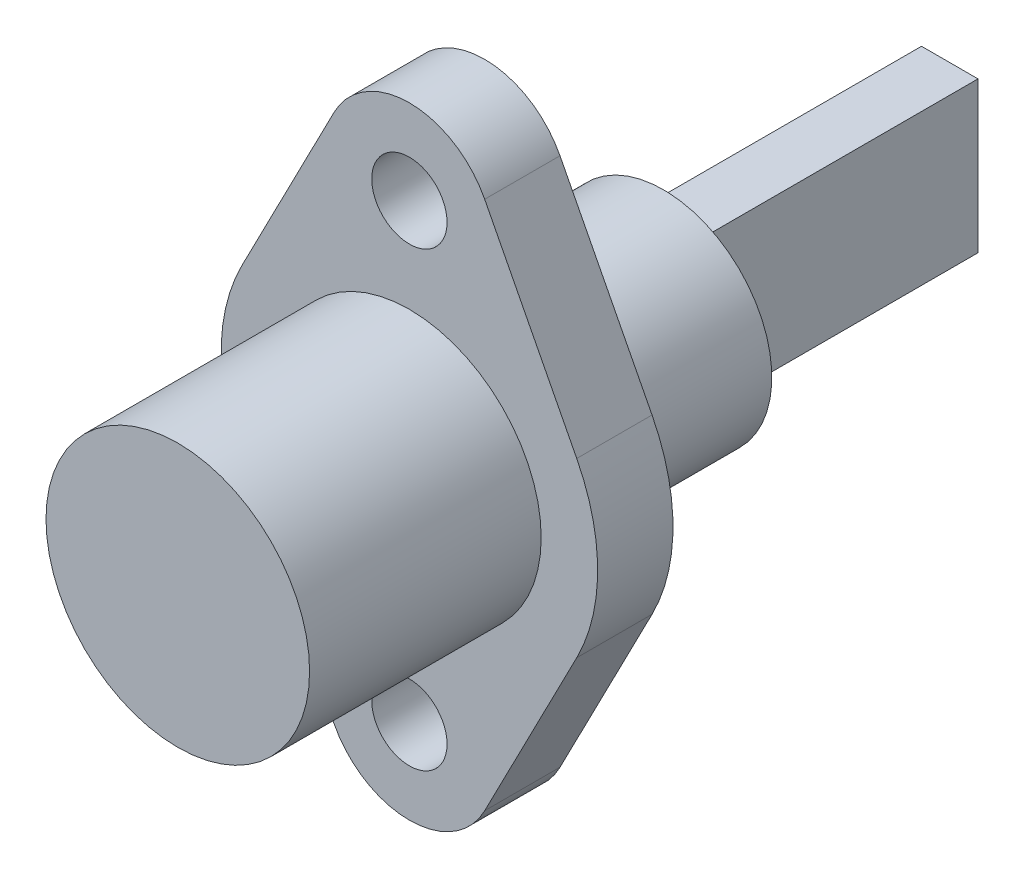
SolidWorks part; units mm, degrees
material "Custom Plastic"
ref_plane "X-Y Datum" through (0, 0, 0) normal (0, 0, 1) x (1, 0, 0)
ref_plane "X-Z Datum" through (0, 0, 0) normal (0, 1, 0) x (1, 0, 0)
ref_plane "Y-Z Datum" through (0, 0, 0) normal (1, 0, 0) x (0, 0, -1)
sketch "Sketch1" plane through (0, 0, 0) normal (0, 0, 1) x (1, 0, 0)
  line L0 (0, 17) -> (0, -17) construction
  line L1 (-10, 0) -> (10, 0) construction
  line L2 (-3.7696, 14.5084) -> (-8.8878, 4.5833)
  line L3 (3.7696, 14.5084) -> (8.8878, 4.5833)
  line L4 (3.7696, -14.5084) -> (8.8878, -4.5833)
  line L5 (-3.7696, -14.5084) -> (-8.8878, -4.5833)
  line L6 (0, 12) -> (0, -12) construction
  circle A0 centre (0, 0) radius 10
  circle A5 centre (0, 12) radius 2
  circle A6 centre (0, -12) radius 2
  circle A7 centre (0, 12) radius 4.5
  circle A8 centre (0, -12) radius 4.5
  point P4 (0, 0)
  point P8 (0, 0)
  point P23 (-4.7908, 14.0744)
  point P24 (-3.3142, -14.2597)
  point P26 (0, 0)
  dimension "D3" = 4
  dimension "D5" = 24
  dimension "D1" = 34
  dimension "D2" = 20
  dimension "D4" = 24
  dimension "D6" = 2.5
extrude "Boss-Extrude1" add sketch "Sketch1" along normal blind 4 contours A7 A0 A5 | A7 L2 A0 | A7 A0 L3 | A0 A8 A7 | A0 A7 | L5 A8 A0 | A8 A0 | A8 A0 A6 | A0 A8 L4 region at (-5.5325, 9.5178, 0) region at (0, 16.3849, 0) region at (0, 0, 0) region at (5.5325, 9.5178, 0) region at (0, 8.8462, 0) region at (-5.5325, -9.5178, 0) region at (-4.3707, -11.6473, 0) region at (0, -8.8462, 0) region at (5.5325, -9.5178, 0)
sketch "Sketch2" plane through (0, 0, 4) normal (0, 0, 1) x (1, 0, 0)
  circle A0 centre (0, 0) radius 7
  dimension "D1" = 14
extrude "Boss-Extrude2" add sketch "Sketch2" along normal blind 12.3
sketch "Sketch3" plane through (0, 0, 0) normal (0, 0, -1) x (-1, 0, 0)
  circle A0 centre (0, 0) radius 7.5
  dimension "D1" = 15
extrude "Boss-Extrude3" add sketch "Sketch3" along normal blind 0.5
sketch "Sketch4" plane through (0, 0, -0.5) normal (0, 0, -1) x (-1, 0, 0)
  line L1 (-1.5, 4) -> (1.5, 4)
  line L2 (-1.5, 4) -> (-1.5, -4)
  line L3 (-1.5, -4) -> (1.5, -4)
  line L4 (1.5, 4) -> (1.5, -4)
  line L5 (-1.5, 4) -> (1.5, -4) construction
  line L6 (-1.5, -4) -> (1.5, 4) construction
  point P0 (0, 0)
  dimension "D1" = 8
  dimension "D2" = 3
extrude "Boss-Extrude4" add sketch "Sketch4" along normal blind 24.2
sketch "Sketch5" plane through (0, 0, -0.5) normal (0, 0, -1) x (-1, 0, 0)
  circle A0 centre (0, 0) radius 5.75
  dimension "D1" = 11.5
extrude "Boss-Extrude5" add sketch "Sketch5" along normal blind 9
